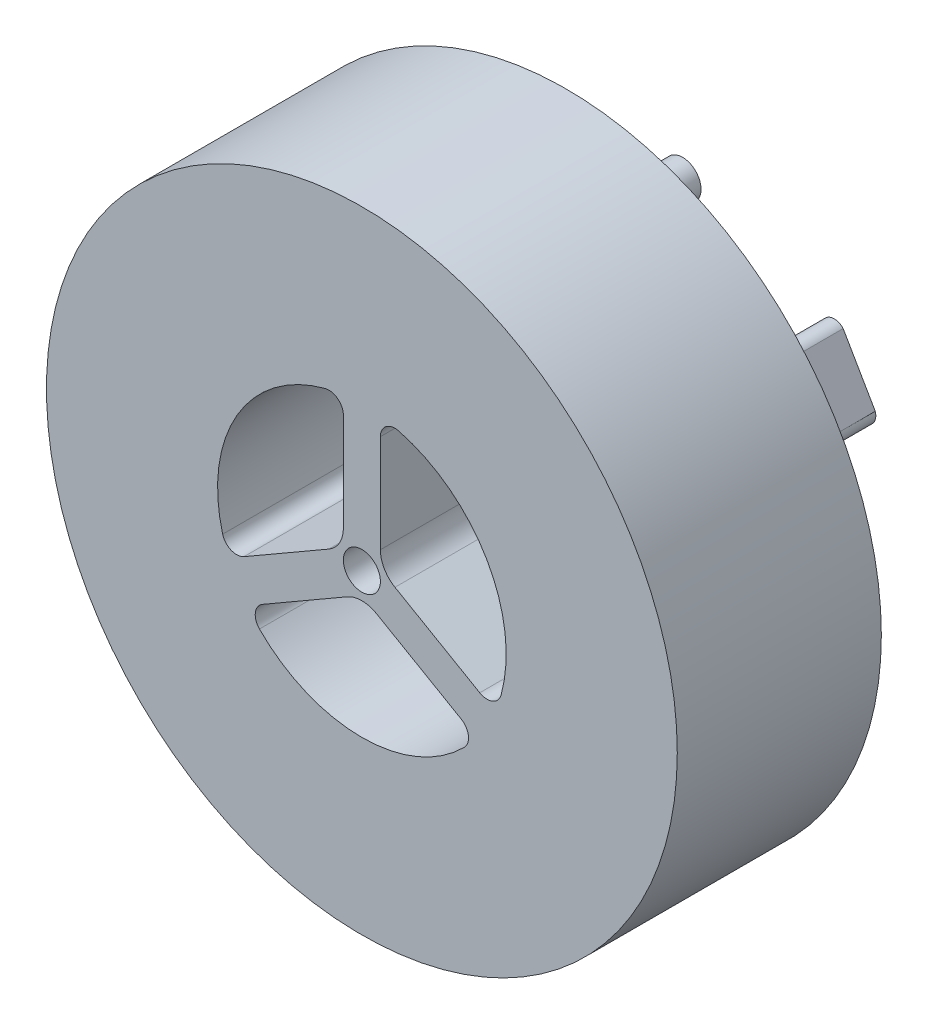
SolidWorks part; units mm, degrees
ref_plane "Front Plane" through (0, 0, 0) normal (0, 0, 1) x (1, 0, 0)
ref_plane "Top Plane" through (0, 0, 0) normal (0, 1, 0) x (1, 0, 0)
ref_plane "Right Plane" through (0, 0, 0) normal (1, 0, 0) x (0, 0, -1)
sketch "Sketch1" plane through (0, 0, 0) normal (0, 0, 1) x (1, 0, 0)
  line L0 (-3.175, 4.7198) -> (-3.175, 21.5141)
  line L1 (3.175, 4.7198) -> (3.175, 21.5141)
  line L2 (5.675, 0.3897) -> (20.2193, -8.0074)
  line L3 (2.5, -5.1095) -> (17.0443, -13.5067)
  line L4 (-2.5, -5.1095) -> (-17.0443, -13.5067)
  line L5 (-5.675, 0.3897) -> (-20.2193, -8.0074)
  line L6 (0, 38.6039) -> (0, -66.8993) construction
  line L7 (26.6303, -15.375) -> (-49.2221, 28.4184) construction
  circle A0 centre (0, 30.75) radius 3.175
  circle A1 centre (26.6303, -15.375) radius 3.175
  arc A2 (17.0443, -13.5067) -> (17.5689, -17.4326) centre (15.7943, -15.6717) cw
  arc A3 (-23.8815, -6.4988) -> (-6.3126, 23.9314) centre (0, 0) cw
  arc A4 (6.3126, 23.9314) -> (23.8815, -6.4988) centre (0, 0) cw
  circle A5 centre (-26.6303, -15.375) radius 3.175
  arc A6 (17.5689, -17.4326) -> (-17.5689, -17.4326) centre (0, 0) cw
  circle A7 centre (0, 0) radius 54.1
  arc A8 (2.5, -5.1095) -> (-2.5, -5.1095) centre (0, -9.4397) ccw
  arc A9 (5.675, 0.3897) -> (3.175, 4.7198) centre (8.175, 4.7198) cw
  arc A10 (-3.175, 4.7198) -> (-5.675, 0.3897) centre (-8.175, 4.7198) cw
  arc A11 (-20.2193, -8.0074) -> (-23.8815, -6.4988) centre (-21.4693, -5.8424) cw
  arc A12 (-17.0443, -13.5067) -> (-17.5689, -17.4326) centre (-15.7943, -15.6717) ccw
  arc A13 (20.2193, -8.0074) -> (23.8815, -6.4988) centre (21.4693, -5.8424) ccw
  arc A14 (3.175, 21.5141) -> (6.3126, 23.9314) centre (5.675, 21.5141) cw
  arc A15 (-6.3126, 23.9314) -> (-3.175, 21.5141) centre (-5.675, 21.5141) cw
  circle A16 centre (0, 0) radius 3.175
  point P14 (0, 0)
  point P26 (0, 0)
  point P31 (0, 0)
  dimension "D1" = 3
  dimension "D3" = 5
  dimension "D4" = 2.5
  dimension "D5" = 2.5
  dimension "D7" = 108.2
  dimension "D2" = 3
  dimension "D6" = 3
extrude "Boss-Extrude1" add sketch "Sketch1" along normal blind 35
sketch "Esquisse1" plane through (0, 0, 35) normal (0, 0, 1) x (1, 0, 0)
  line L0 (0, 45.3911) -> (0, -60.0658) construction
  line L1 (-26.6303, -15.375) -> (60.0009, 34.6415) construction
  line L2 (-33.1044, 19.1129) -> (26.6303, -15.375) construction
  line L4 (-21.3945, 15.1868) -> (-23.8494, 10.9348)
  line L5 (-33.0534, 12.7263) -> (-30.3007, 17.4941)
  line L6 (-30.3007, 17.4941) -> (-27.548, 22.262)
  arc A6 (-23.8494, 10.9348) -> (-28.3284, 9.4031) centre (-26.9661, 12.7342) cw
  arc A7 (-28.3284, 9.4031) -> (-31.1339, 10.0059) centre (-31.4201, 1.8433) ccw
  arc A8 (-31.1339, 10.0059) -> (-33.0534, 12.7263) centre (-31.0606, 12.095) cw
  arc A9 (-24.2323, 21.9598) -> (-27.548, 22.262) centre (-26.0049, 20.8518) ccw
  arc A10 (-21.3945, 15.1868) -> (-22.3076, 19.8316) centre (-24.5112, 16.9862) ccw
  arc A11 (-22.3076, 19.8316) -> (-24.2323, 21.9598) centre (-17.3064, 26.289) cw
  point P24 (-22.6219, 13.0608)
ref_axis "Axe1" through (0, 0, 35) along (0, 0, -1)
extrude "Boss.-Extru.3" add sketch "Esquisse1" against normal blind 20 from surface starting at face at (-11.3286, 6.5406, 0)
pattern_circular "Répétition circulaire3" count 3 every 120 about axis through (0, 0, 35) along (0, 0, -1) of "Boss.-Extru.3"
sketch "Esquisse3" plane through (0, 0, 35) normal (0, 0, 1) x (1, 0, 0)
  line L0 (0, 43.233) -> (0, -57.4762) construction
  circle A0 centre (0, 30.75) radius 3.175
extrude "Boss.-Extru.4" add sketch "Esquisse3" against normal blind 55
pattern_circular "Répétition circulaire4" count 3 every 120 about axis through (0, 0, 35) along (0, 0, -1) of "Boss.-Extru.4"
sketch "Esquisse4" plane through (0, 0, 35) normal (0, 0, 1) x (1, 0, 0)
  circle A0 centre (0, 0) radius 3.175
scale "Echelle1" scale about centroid uniform scaling yes scale factor 2
equation "\"8ta\"= 10"
equation "\"D1@Boss.-Extru.3\"=\"8ta\"+10"
